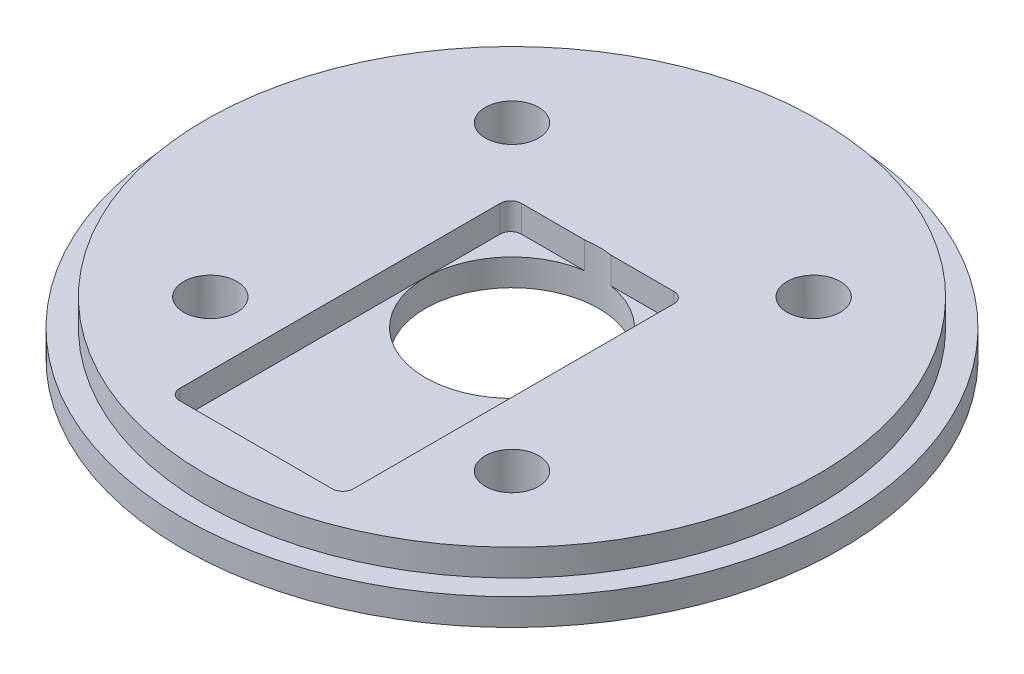
SolidWorks part; units mm, degrees
ref_plane "Front Plane" through (0, 0, 0) normal (0, 0, 1) x (1, 0, 0)
ref_plane "Top Plane" through (0, 0, 0) normal (0, 1, 0) x (1, 0, 0)
ref_plane "Right Plane" through (0, 0, 0) normal (1, 0, 0) x (0, 0, -1)
sketch "Sketch2" plane through (0, 0, 0) normal (0, 1, 0) x (1, 0, 0)
  circle A0 centre (0, 0) radius 39.243
  dimension "D1" = 78.486
extrude "Boss-Extrude1" add sketch "Sketch2" along normal blind 6.35
sketch "Sketch4" plane through (0, 6.35, 0) normal (0, 1, 0) x (1, 0, 0)
  circle A0 centre (0, 0) radius 36.5125
  circle A1 centre (0, 0) radius 39.243 construction
  circle A2 centre (0, 0) radius 39.243
  dimension "D1" = 73.025
extrude "Cut-Extrude1" cut sketch "Sketch4" against normal blind 3.175
sketch "Sketch5" plane through (0, 6.35, 0) normal (0, 1, 0) x (1, 0, 0)
  line L0 (17.9605, 17.9605) -> (-17.9605, -17.9605) construction
  line L1 (-17.9605, 17.9605) -> (17.9605, -17.9605) construction
  line L2 (-1000, 0) -> (49000, 0) construction
  point P1 (-17.9605, -17.9605)
  point P2 (17.9605, 17.9605)
  point P5 (17.9605, -17.9605)
  point P6 (-17.9605, 17.9605)
  dimension "D1" = 50.8
  dimension "D2" = 45
hole_wizard "1/4 (0.25) Diameter Hole1" positions "Sketch5" profile "Sketch6" hole size "1/4" standard "ANSI Inch" end condition through all
sketch "Sketch6" plane through (-17.9605, 6.35, -17.9605) normal (1, 0, 0) x (0, 0, 1)
  line L0 (0, 0) -> (0, 6.35)
  line L1 (0, 6.35) -> (3.175, 6.35)
  line L2 (3.175, 6.35) -> (3.175, 0)
  line L5 (3.175, 0) -> (0, 0)
  line L11 (0, -6.35) -> (0, 107.95) construction
  dimension "Thru Hole Dia." = 6.35
  dimension "Thru Hole Depth" = 6.35
sketch "Sketch7" plane through (0, 6.35, 0) normal (0, 1, 0) x (1, 0, 0)
  point P0 (0, 0)
hole_wizard "13/16 (0.8125) Diameter Hole1" positions "Sketch7" profile "Sketch8" hole size "13/16" standard "ANSI Inch" end condition through all
sketch "Sketch8" plane through (0, 6.35, 0) normal (1, 0, 0) x (0, 0, 1)
  line L0 (0, 0) -> (0, 6.35)
  line L1 (0, 6.35) -> (10.3187, 6.35)
  line L2 (10.3187, 6.35) -> (10.3187, 0)
  line L5 (10.3187, 0) -> (0, 0)
  line L11 (0, -6.35) -> (0, 107.95) construction
  dimension "Thru Hole Dia." = 20.6375
  dimension "Thru Hole Depth" = 6.35
sketch "Sketch9" plane through (0, 0, 0) normal (0, -1, 0) x (1, 0, 0)
  circle A0 centre (-17.9605, -17.9605) radius 3.175 construction
  circle A1 centre (17.9605, -17.9605) radius 3.175 construction
  circle A2 centre (17.9605, 17.9605) radius 3.175 construction
  circle A3 centre (-17.9605, 17.9605) radius 3.175 construction
  circle A4 centre (-17.9605, -17.9605) radius 3.175 construction
  circle A5 centre (17.9605, -17.9605) radius 3.175 construction
  circle A6 centre (17.9605, 17.9605) radius 3.175 construction
  circle A7 centre (-17.9605, 17.9605) radius 3.175 construction
  circle A8 centre (-17.9605, 17.9605) radius 6.0325
  circle A9 centre (17.9605, 17.9605) radius 6.0325
  circle A10 centre (17.9605, -17.9605) radius 6.0325
  circle A11 centre (-17.9605, -17.9605) radius 6.0325
  point P13 (-17.9605, 17.9605)
  point P14 (17.9605, 17.9605)
  point P15 (17.9605, -17.9605)
  point P16 (-17.9605, -17.9605)
  dimension "D1" = 12.065
extrude "Cut-Extrude2" cut sketch "Sketch9" against normal blind 1.5875
sketch "Sketch11" plane through (0, 6.35, 0) normal (0, 1, 0) x (1, 0, 0)
  line L1 (-10.35, 10.2) -> (10.35, 10.2)
  line L2 (-10.35, 10.2) -> (-10.35, -30.5)
  line L3 (-10.35, -30.5) -> (10.35, -30.5)
  line L4 (10.35, 10.2) -> (10.35, -30.5)
  line L5 (-10.35, 10.2) -> (10.35, -30.5) construction
  line L6 (-10.35, -30.5) -> (10.35, 10.2) construction
  point P0 (0, 0)
  point P1 (0, -10.15)
  dimension "D1" = 10.2
  dimension "D2" = 20.7
  dimension "D3" = 40.7
extrude "Cut-Extrude3" cut sketch "Sketch11" against normal blind 3.175
fillet "Fillet1" radius 1.27 4 edges at (-10.35, 4.7625, -10.2) (-10.35, 4.7625, 30.5) (10.35, 4.7625, 30.5) (10.35, 4.7625, -10.2)
equation "\"AIRFRAME_OD\"= 3.142in"
equation "\"AIRFRAME_ID\"= 3.00in"
equation "\"FLAT_T\"= 0.125in"
equation "\"NOSE_EXP_L\"= 3.5in"
equation "\"NOSE_SHOULDER_L\"= 1.5in"
equation "\"MAIN_L\"= 30in"
equation "\"RECO_COUP_L\"= 6in"
equation "\"RECO_SWITCH_L\"= 1.5in"
equation "\"DROGUE_L\"= 14in"
equation "\"ATS_FORE_COUP_L\"= 4in"
equation "\"ATS_AFT_COUP_L\"= 2.5in"
equation "\"LOWER_L\"= 16in"
equation "\"FIN_N\"= 4"
equation "\"CR_AFT_X\"= 0.5in"
equation "\"CR_FORE_X\"= 6in"
equation "\"D1@Boss-Extrude1\"=2*\"FLAT_T\""
equation "\"COUPLER_OD\"= 2.998in"
equation "\"COUPLER_ID\"= 2.875in"
equation "\"RECO_ROD_X\"= 1.5in"
equation "\"ATS_ROD_X\"= 2in"
equation "\"FIN_ROOT\"= 5in"
equation "\"FIN_X\"= 0.75in"
equation "\"MOTOR_OD\"= 2.25in"
equation "\"MOTOR_ID\"= 2.126in"
equation "\"MOTOR_L\"= 8in"
equation "\"MOTOR_LOWER_X\"= 0.5in"
equation "\"D1@Sketch4\"=\"COUPLER_ID\""
equation "\"D1@Cut-Extrude1\"=\"FLAT_T\""
equation "\"D1@Cut-Extrude3\"=\"FLAT_T\""
